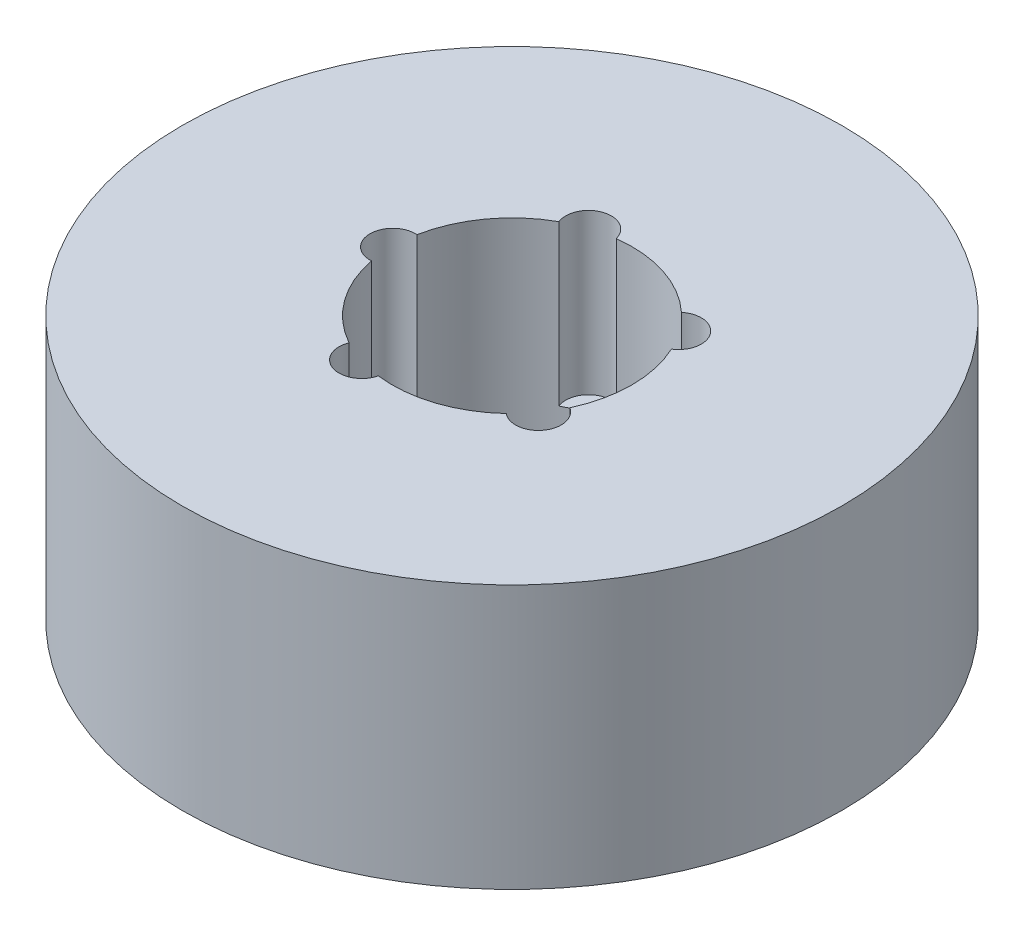
SolidWorks part; units mm, degrees
ref_plane "Front Plane" through (0, 0, 0) normal (0, 0, 1) x (1, 0, 0)
ref_plane "Top Plane" through (0, 0, 0) normal (0, 1, 0) x (1, 0, 0)
ref_plane "Right Plane" through (0, 0, 0) normal (1, 0, 0) x (0, 0, -1)
sketch "Sketch1" plane through (0, 0, 0) normal (0, 1, 0) x (1, 0, 0)
  circle A0 centre (0, 0) radius 27.5
  dimension "FLANGE_OD" = 55
extrude "Boss-Extrude1" add sketch "Sketch1" along normal blind 22
sketch "Sketch2" plane through (0, 0, 0) normal (0, 1, 0) x (1, 0, 0)
  circle A0 centre (0, 0) radius 10
  dimension "BORE_D" = 20
extrude "Cut-Extrude1" cut sketch "Sketch2" along normal through all
sketch "Sketch3" plane through (0, 22, 0) normal (0, 1, 0) x (1, 0, 0)
  circle A0 centre (0, 0) radius 9.9428 construction
  circle A1 centre (-9.9428, 0) radius 1.9024
  dimension "BOLT_D" = 3.8048
  dimension "BOLT_PCD" = 19.8856
extrude "Cut-Extrude2" cut sketch "Sketch3" against normal blind 13.3169
pattern_circular "CirPattern1" count 5 over 360 about axis through (0, 0, 0) along (0, 1, 0) of "Cut-Extrude2"
